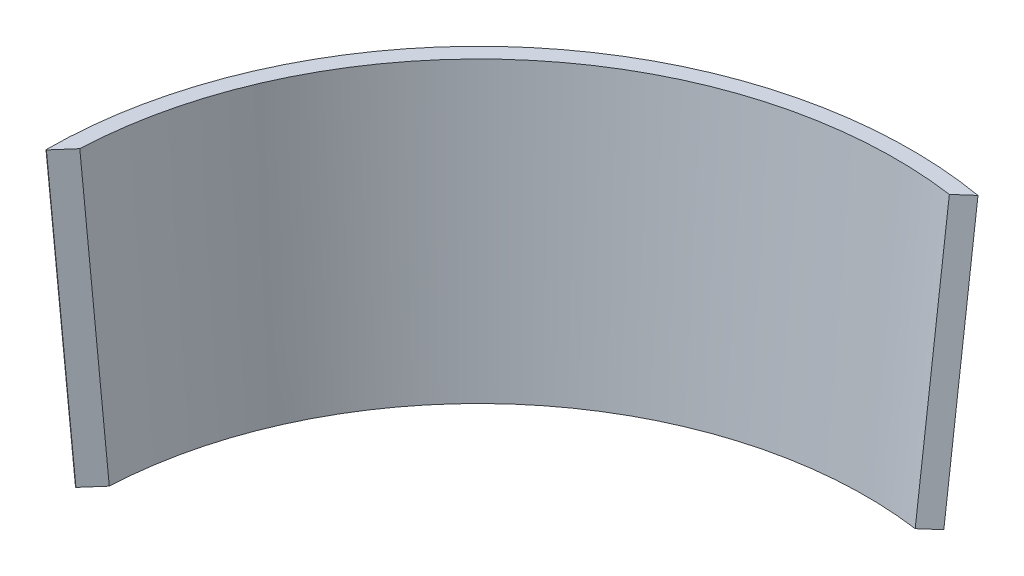
SolidWorks part; units mm, degrees
ref_plane "Plan de face" through (0, 0, 0) normal (0, 0, 1) x (1, 0, 0)
ref_plane "Plan de dessus" through (0, 0, 0) normal (0, 1, 0) x (1, 0, 0)
ref_plane "Plan de droite" through (0, 0, 0) normal (1, 0, 0) x (0, 0, -1)
sketch "Esquisse2" plane through (0, 0, 0) normal (0, 1, 0) x (1, 0, 0)
  line L0 (0, 0) -> (-33.2568, 0) construction
  line L1 (0, 0) -> (-29.5861, 29.5861) construction
  line L2 (0, 0) -> (-21.7323, -21.7323) construction
  line L3 (-18.3848, -18.3848) -> (-16.2635, -16.2635)
  line L4 (-18.3848, 18.3848) -> (-16.2635, 16.2635)
  circle A0 centre (0, 0) radius 23 construction
  circle A1 centre (0, 0) radius 26 construction
  arc A2 (-16.2635, 16.2635) -> (-16.2635, -16.2635) centre (0, 0) ccw
  arc A3 (-18.3848, 18.3848) -> (-18.3848, -18.3848) centre (0, 0) ccw
  dimension "D1" = 3
  dimension "D2" = 52
  dimension "D3" = 45
  dimension "D4" = 45
extrude "Boss.-Extru.1" [suppressed] add sketch "Esquisse2" along normal blind 20
chamfer "Chanfrein1" [suppressed] distance 20 angle 6.07
sketch "Esquisse3" plane through (0, 0, 0) normal (0, 0, 1) x (1, 0, 0)
  line L0 (-8.3173, 0) -> (8.3173, 0) construction
  line L1 (-24.9944, 0) -> (-26, 0)
  line L2 (-26, 0) -> (-27.9034, 17.8991)
  line L3 (-27.9034, 17.8991) -> (-26.8977, 17.8991)
  line L4 (-26.8977, 17.8991) -> (-24.9944, 0)
  line L6 (0, 7.4935) -> (0, -7.4935) construction
  point P5 (0, 0)
  point P8 (-4.5004, 0.8311)
  dimension "D1" = 1
  dimension "D2" = 18
  dimension "D3" = 6.07
  dimension "D4" = 26
revolve "Révolution1" add sketch "Esquisse3" angle 100 about L6
chamfer "Chanfrein2" distance 1 angle 50 2 edges at (4.5055, 8.9495, -25.5519) (-25.9461, 8.9495, 0) first distance on face at (-13.699, 8.9495, -16.3259) first distance on face at (-26.4489, 8.9495, 0)
